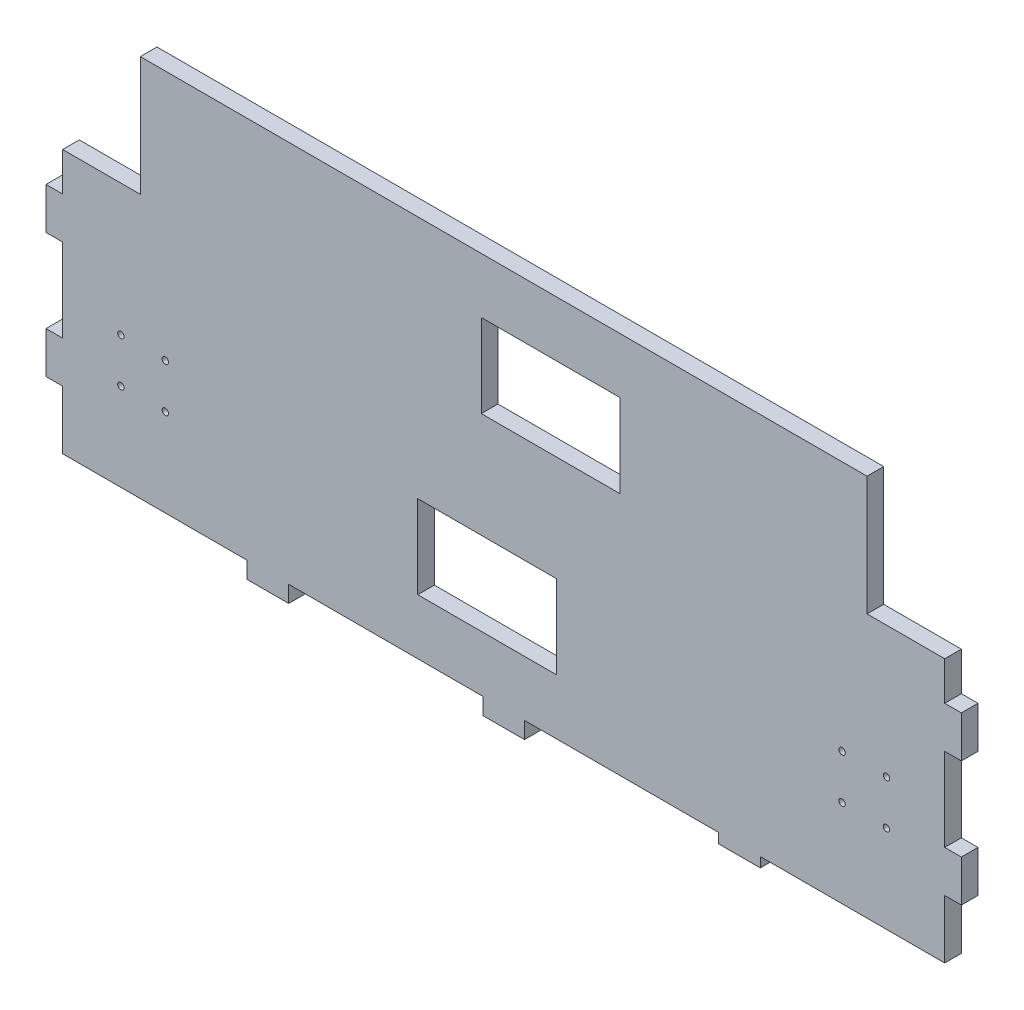
SolidWorks part; units mm, degrees
ref_plane "Plan de face" through (0, 0, 0) normal (0, 0, 1) x (1, 0, 0)
ref_plane "Plan de dessus" through (0, 0, 0) normal (0, 1, 0) x (1, 0, 0)
ref_plane "Plan de droite" through (0, 0, 0) normal (1, 0, 0) x (0, 0, -1)
sketch "Esquisse1" plane through (0, 0, 0) normal (0, 0, 1) x (1, 0, 0)
  line L0 (-159, 35) -> (-131, 35)
  line L1 (0, 102.0551) -> (0, -193.4247) construction
  line L2 (-159, 35) -> (-159, -60)
  line L3 (-159, -60) -> (159, -60)
  line L4 (159, 35) -> (159, -60)
  line L6 (131, 35) -> (131, 78)
  line L7 (131, 78) -> (-131, 78)
  line L8 (-131, 35) -> (-131, 78)
  line L9 (159, 35) -> (131, 35)
  line L10 (19, -10) -> (-31, -10)
  line L11 (19, -10) -> (19, -40)
  line L12 (19, -40) -> (-31, -40)
  line L13 (-31, -10) -> (-31, -40)
  line L14 (41.9165, 58) -> (-8.0835, 58)
  line L15 (41.9165, 58) -> (41.9165, 28)
  line L16 (41.9165, 28) -> (-8.0835, 28)
  line L17 (-8.0835, 58) -> (-8.0835, 28)
  dimension "D1" = 95
  dimension "D2" = 28
  dimension "D3" = 28
  dimension "D4" = 95
  dimension "D6" = 262
  dimension "D7" = 138
  dimension "D5" = 159
  dimension "D8" = 318
  dimension "D9" = 30
  dimension "D10" = 50
  dimension "D11" = 20
  dimension "D12" = 140
  dimension "D13" = 30
  dimension "D14" = 50
  dimension "D15" = 20
extrude "Boss.-Extru.1" add sketch "Esquisse1" along normal blind 6
sketch "Esquisse2" plane through (0, 0, 6) normal (0, 0, 1) x (1, 0, 0)
  line L0 (-159, -60) -> (159, -60) construction
  line L1 (-92.5, -60) -> (-77.5, -60)
  line L2 (-92.5, -60) -> (-92.5, -66)
  line L3 (-92.5, -66) -> (-77.5, -66)
  line L4 (-77.5, -60) -> (-77.5, -66)
  line L5 (-159, 35) -> (-159, -60) construction
  line L6 (-7.5, -60) -> (7.5, -60)
  line L7 (-7.5, -60) -> (-7.5, -66)
  line L8 (-7.5, -66) -> (7.5, -66)
  line L9 (7.5, -60) -> (7.5, -66)
  line L10 (77.5, -60) -> (92.5, -60)
  line L11 (77.5, -60) -> (77.5, -63.5535)
  line L12 (77.5, -63.5535) -> (92.5, -63.5535)
  line L13 (92.5, -60) -> (92.5, -63.5535)
  line L15 (0, 107.6082) -> (0, -117.4775) construction
  line L16 (-131, 35) -> (-159, 35) construction
  line L17 (-159, 21.09) -> (-165, 21.09)
  line L18 (-159, 21.09) -> (-159, 6.09)
  line L19 (-159, 6.09) -> (-165, 6.09)
  line L20 (-165, 21.09) -> (-165, 6.09)
  line L21 (-159, -23.91) -> (-165, -23.91)
  line L22 (-159, -23.91) -> (-159, -38.91)
  line L23 (-159, -38.91) -> (-165, -38.91)
  line L24 (-165, -23.91) -> (-165, -38.91)
  line L25 (165, -23.91) -> (165, -38.91)
  line L26 (159, -38.91) -> (165, -38.91)
  line L27 (159, -23.91) -> (159, -38.91)
  line L28 (159, -23.91) -> (165, -23.91)
  line L29 (165, 21.09) -> (165, 6.09)
  line L30 (159, 6.09) -> (165, 6.09)
  line L31 (159, 21.09) -> (159, 6.09)
  line L32 (159, 21.09) -> (165, 21.09)
  dimension "D1" = 66.5
  dimension "D2" = 70
  dimension "D3" = 15
  dimension "D4" = 15
  dimension "D5" = 70
  dimension "D6" = 15
  dimension "D7" = 6
  dimension "D8" = 6
  dimension "D9" = 6
  dimension "D10" = 6
  dimension "D11" = 13.91
  dimension "D12" = 15
  dimension "D13" = 30
  dimension "D14" = 15
extrude "Boss.-Extru.2" add sketch "Esquisse2" against normal blind 6
sketch "Esquisse3" plane through (0, 0, 0) normal (0, 0, -1) x (-1, 0, 0)
  line L0 (159, -60) -> (92.5, -60) construction
  line L1 (159, 6.09) -> (159, -23.91) construction
  line L2 (0, 141.59) -> (0, -167.3887) construction
  circle A0 centre (138, -28.38) radius 1.15
  circle A1 centre (138, -12.38) radius 1.15
  circle A2 centre (122, -12.38) radius 1.15
  circle A3 centre (122, -28.38) radius 1.15
  circle A4 centre (-122, -28.38) radius 1.15
  circle A5 centre (-122, -12.38) radius 1.15
  circle A6 centre (-138, -12.38) radius 1.15
  circle A7 centre (-138, -28.38) radius 1.15
  dimension "D1" = 31.62
  dimension "D2" = 21
  dimension "D7" = 2.3
  dimension "D8" = 2.3
  dimension "D9" = 2.3
  dimension "D10" = 2.3
  dimension "D3" = 16
  dimension "D4" = 16
  dimension "D5" = 16
  dimension "D6" = 16
extrude "Enlèv. mat.-Extru.1" cut sketch "Esquisse3" against normal blind 6
equation "\"D5@Esquisse1\"=\"D8@Esquisse1\"/2"
